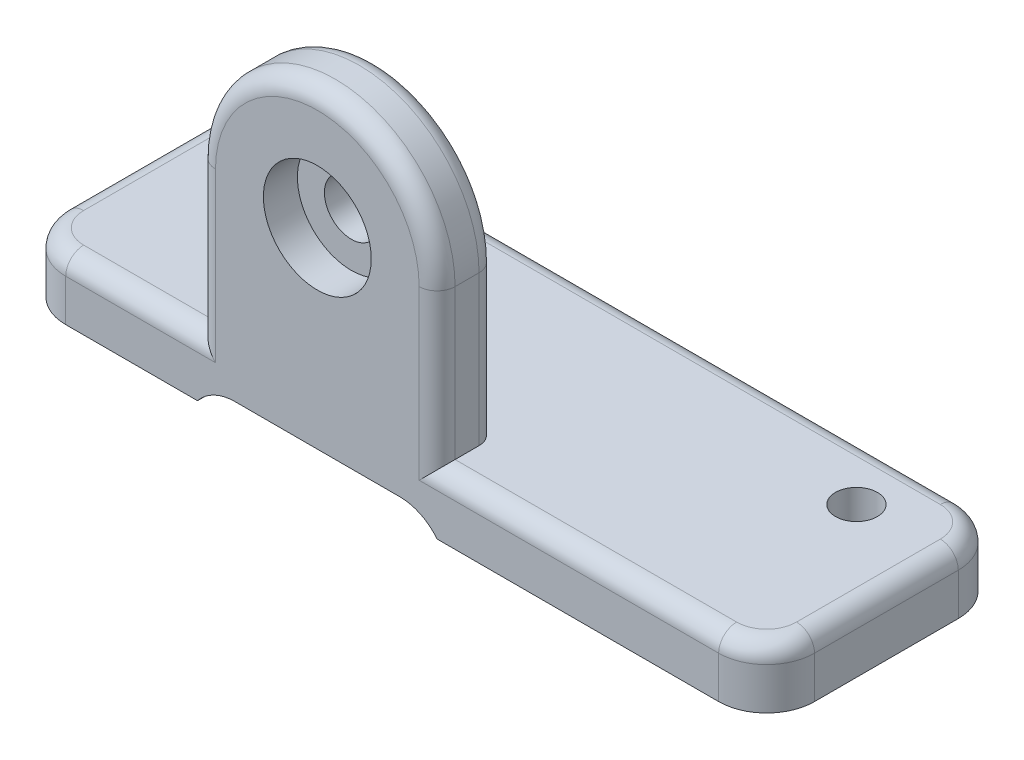
SolidWorks part; units mm, degrees
ref_plane "Front Plane" through (0, 0, 0) normal (0, 0, 1) x (1, 0, 0)
ref_plane "Top Plane" through (0, 0, 0) normal (0, 1, 0) x (1, 0, 0)
ref_plane "Right Plane" through (0, 0, 0) normal (1, 0, 0) x (0, 0, -1)
sketch "Sketch2" plane through (0, 0, 0) normal (0, 1, 0) x (1, 0, 0)
  line L5 (0, 0) -> (125, 0)
  line L6 (0, 0) -> (0, 40)
  line L7 (0, 40) -> (125, 40)
  line L8 (125, 0) -> (125, 40)
  dimension "D1" = 125
  dimension "D2" = 40
extrude "Boss-Extrude1" add sketch "Sketch2" along normal blind 10
sketch "Sketch3" plane through (0, 0, 0) normal (0, 0, 1) x (1, 0, 0)
  line L0 (0, 0) -> (125, 0) construction
  line L1 (0, 10) -> (0, 0) construction
  line L2 (30, 35) -> (30, 0)
  line L3 (30, 0) -> (70, 0)
  line L4 (70, 0) -> (70, 35)
  arc A0 (70, 35) -> (30, 35) centre (50, 35) ccw
  point P0 (50, 35)
  dimension "D3" = 20
  dimension "D1" = 35
  dimension "D2" = 50
extrude "Boss-Extrude2" add sketch "Sketch3" against normal blind 10
sketch "Sketch4" plane through (0, 0, 0) normal (0, 0, 1) x (1, 0, 0)
  line L0 (0, 0) -> (125, 0) construction
  line L1 (30, 0) -> (70, 0)
  line L2 (30, 0) -> (30, 3)
  line L3 (30, 3) -> (70, 3)
  line L4 (70, 0) -> (70, 3)
  dimension "D1" = 3
extrude "Cut-Extrude1" cut sketch "Sketch4" against normal blind 80
hole_wizard "CBORE for M8 Hex Head Bolt1" positions "3DSketch1" profile "Sketch5" counterbore size "M8" standard "ANSI Metric" end condition through all
sketch3d "3DSketch1"
  line L0 (50, 35, -10) -> (50, 35, 0) construction
  point P0 (50, 35, 0)
sketch "Sketch5" plane through (50, 35, 0) normal (1, 0, 0) x (0, -1, 0)
  line L0 (0, 0) -> (0, 40)
  line L1 (0, 40) -> (4.5, 40)
  line L3 (4.5, 40) -> (4.5, 5.68)
  line L4 (4.5, 5.68) -> (9.005, 5.68)
  line L5 (9.005, 5.68) -> (9.005, 0)
  line L7 (9.005, 0) -> (0, 0)
  line L11 (0, -6.35) -> (0, 107.95) construction
  dimension "Thru Hole Dia." = 9
  dimension "Thru Hole Depth" = 40
  dimension "C'Bore Dia." = 18.01
  dimension "C'Bore Depth" = 5.68
fillet "Fillet2" radius 8 6 edges at (125, 5, 0) (125, 5, -40) (0, 5, -40) (0, 5, 0) (70, 3, -20) (30, 3, -20)
fillet "Fillet3" radius 3 15 edges at (19, 10, 0) (2.3431, 10, -2.3431) (0, 10, -20) (2.3431, 10, -37.6569) (62.5, 10, -40) (122.6569, 10, -37.6569) (125, 10, -20) (122.6569, 10, -2.3431) (30, 22.5, -10) (50, 55, -10) (30, 22.5, 0) (50, 55, 0) (93.5, 10, 0) (70, 22.5, -10) (70, 22.5, 0)
sketch "Sketch6" plane through (0, 10, 0) normal (0, 1, 0) x (1, 0, 0)
  line L0 (0, 8) -> (0, 32) construction
  line L1 (8, 40) -> (117, 40) construction
  line L2 (125, 32) -> (125, 8) construction
  point P0 (15, 30)
  point P6 (110, 30)
  dimension "D1" = 15
  dimension "D2" = 10
  dimension "D3" = 15
hole_wizard "Ø7.0 (7) Diameter Hole1" positions "3DSketch2" profile "Sketch7" hole size "Ø7.0" standard "AS" end condition through all
sketch3d "3DSketch2"
  point P0 (15, 10, -30)
  point P3 (110, 10, -30)
sketch "Sketch7" plane through (15, 10, -30) normal (1, 0, 0) x (0, 0, 1)
  line L0 (0, 0) -> (0, 10)
  line L1 (0, 10) -> (3.5, 10)
  line L2 (3.5, 10) -> (3.5, 0)
  line L5 (3.5, 0) -> (0, 0)
  line L11 (0, -6.35) -> (0, 107.95) construction
  dimension "Thru Hole Dia." = 7
  dimension "Thru Hole Depth" = 10
